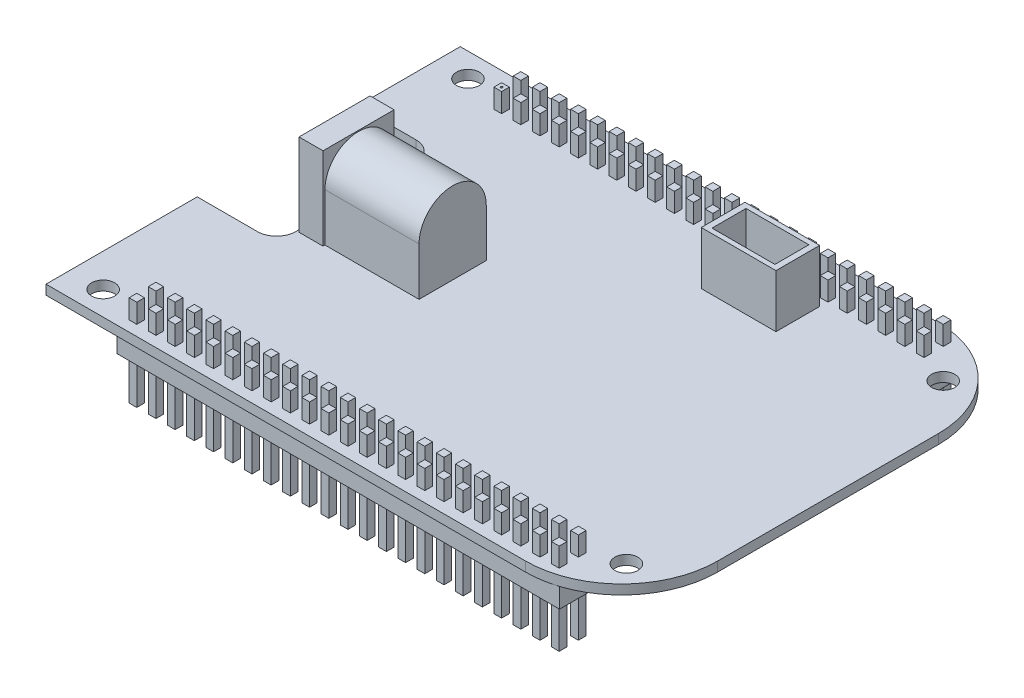
SolidWorks part; units mm, degrees
material "cape"
ref_plane "Front Plane" through (0, 0, 0) normal (0, 0, 1) x (1, 0, 0)
ref_plane "Top Plane" through (0, 0, 0) normal (0, 1, 0) x (1, 0, 0)
ref_plane "Right Plane" through (0, 0, 0) normal (1, 0, 0) x (0, 0, -1)
sketch "Sketch1" plane through (0, 0, 0) normal (0, 1, 0) x (1, 0, 0)
  line L0 (-86.36, 27.305) -> (0, 27.305) construction
  line L1 (-12.7, 0) -> (-80.01, 0)
  line L2 (0, 12.7) -> (0, 41.91)
  line L3 (-12.7, 54.61) -> (-80.01, 54.61)
  line L4 (-86.36, 6.35) -> (-86.36, 48.26)
  line L5 (-71.755, 51.435) -> (-71.755, 3.175) construction
  line L6 (-5.715, 6.35) -> (-5.715, 48.26) construction
  arc A0 (0, 12.7) -> (-12.7, 0) centre (-12.7, 12.7) cw
  arc A1 (0, 41.91) -> (-12.7, 54.61) centre (-12.7, 41.91) ccw
  arc A2 (-86.36, 6.35) -> (-80.01, 0) centre (-80.01, 6.35) ccw
  arc A3 (-86.36, 48.26) -> (-80.01, 54.61) centre (-80.01, 48.26) cw
  circle A4 centre (-71.755, 51.435) radius 1.524
  circle A5 centre (-71.755, 3.175) radius 1.524
  circle A6 centre (-5.715, 6.35) radius 1.524
  circle A7 centre (-5.715, 48.26) radius 1.524
  point P7 (0, 0)
  point P10 (0, 54.61)
  point P13 (-86.36, 0)
  point P26 (-5.715, 27.305)
  point P27 (-71.755, 27.305)
  dimension "D3" = 12.7
  dimension "D4" = 6.35
  dimension "D6" = 41.91
  dimension "D9" = 3.048
  dimension "D1" = 86.36
  dimension "D2" = 54.61
  dimension "D5" = 48.26
  dimension "D7" = 5.715
  dimension "D8" = 14.605
extrude "Boss-Extrude1" add sketch "Sketch1" along normal blind 1.27
sketch "Sketch2" plane through (0, 1.27, 0) normal (0, 1, 0) x (1, 0, 0)
  line L0 (-80.01, 0) -> (-12.7, 0) construction
  line L1 (-5.715, 6.35) -> (-71.755, 6.35) construction
  line L3 (-86.36, 48.26) -> (-86.36, 6.35) construction
  line L4 (-5.715, 48.26) -> (-5.715, 6.35) construction
  circle A2 centre (-5.715, 48.26) radius 1.524
  circle A3 centre (-5.715, 6.35) radius 1.524
  dimension "D2" = 41.91
  dimension "D3" = 6.35
  dimension "D5" = 80.645
sketch "Sketch3" plane through (0, 1.27, 0) normal (0, 1, 0) x (1, 0, 0)
  line L0 (-10.16, 48.895) -> (-10.16, 50.165) construction
  line L1 (-67.31, 53.975) -> (-8.89, 53.975) construction
  line L2 (-67.31, 53.975) -> (-67.31, 48.895) construction
  line L3 (-67.31, 48.895) -> (-8.89, 48.895) construction
  line L4 (-8.89, 53.975) -> (-8.89, 48.895) construction
  line L5 (-86.36, 27.305) -> (0, 27.305) construction
  line L6 (0, 12.7) -> (0, 41.91) construction
  line L7 (-66.548, 4.953) -> (-66.548, 3.937)
  line L8 (-66.548, 4.953) -> (-65.532, 4.953)
  line L9 (-10.16, 50.165) -> (-10.16, 52.705) construction
  line L10 (-10.16, 52.705) -> (-10.16, 53.975) construction
  line L11 (-13.208, 52.197) -> (-12.192, 52.197)
  line L12 (-10.668, 53.213) -> (-9.652, 53.213)
  line L13 (-10.668, 53.213) -> (-10.668, 52.197)
  line L14 (-10.668, 52.197) -> (-9.652, 52.197)
  line L15 (-9.652, 53.213) -> (-9.652, 52.197)
  line L16 (-10.668, 53.213) -> (-9.652, 52.197) construction
  line L17 (-10.668, 52.197) -> (-9.652, 53.213) construction
  line L18 (-10.668, 49.657) -> (-9.652, 49.657)
  line L19 (-10.668, 49.657) -> (-10.668, 50.673)
  line L20 (-10.668, 50.673) -> (-9.652, 50.673)
  line L21 (-9.652, 49.657) -> (-9.652, 50.673)
  line L22 (-10.668, 49.657) -> (-9.652, 50.673) construction
  line L23 (-10.668, 50.673) -> (-9.652, 49.657) construction
  line L24 (-13.208, 53.213) -> (-13.208, 52.197)
  line L25 (-13.208, 53.213) -> (-12.192, 53.213)
  line L26 (-12.192, 53.213) -> (-12.192, 52.197)
  line L27 (-13.208, 50.673) -> (-12.192, 50.673)
  line L28 (-12.192, 49.657) -> (-12.192, 50.673)
  line L29 (-13.208, 49.657) -> (-12.192, 49.657)
  line L30 (-13.208, 49.657) -> (-13.208, 50.673)
  line L31 (-15.748, 52.197) -> (-14.732, 52.197)
  line L32 (-15.748, 53.213) -> (-15.748, 52.197)
  line L33 (-15.748, 53.213) -> (-14.732, 53.213)
  line L34 (-14.732, 53.213) -> (-14.732, 52.197)
  line L35 (-15.748, 50.673) -> (-14.732, 50.673)
  line L36 (-14.732, 49.657) -> (-14.732, 50.673)
  line L37 (-15.748, 49.657) -> (-14.732, 49.657)
  line L38 (-15.748, 49.657) -> (-15.748, 50.673)
  line L39 (-18.288, 52.197) -> (-17.272, 52.197)
  line L40 (-18.288, 53.213) -> (-18.288, 52.197)
  line L41 (-18.288, 53.213) -> (-17.272, 53.213)
  line L42 (-17.272, 53.213) -> (-17.272, 52.197)
  line L43 (-18.288, 50.673) -> (-17.272, 50.673)
  line L44 (-17.272, 49.657) -> (-17.272, 50.673)
  line L45 (-18.288, 49.657) -> (-17.272, 49.657)
  line L46 (-18.288, 49.657) -> (-18.288, 50.673)
  line L47 (-20.828, 52.197) -> (-19.812, 52.197)
  line L48 (-20.828, 53.213) -> (-20.828, 52.197)
  line L49 (-20.828, 53.213) -> (-19.812, 53.213)
  line L50 (-19.812, 53.213) -> (-19.812, 52.197)
  line L51 (-20.828, 50.673) -> (-19.812, 50.673)
  line L52 (-19.812, 49.657) -> (-19.812, 50.673)
  line L53 (-20.828, 49.657) -> (-19.812, 49.657)
  line L54 (-20.828, 49.657) -> (-20.828, 50.673)
  line L55 (-23.368, 52.197) -> (-22.352, 52.197)
  line L56 (-23.368, 53.213) -> (-23.368, 52.197)
  line L57 (-23.368, 53.213) -> (-22.352, 53.213)
  line L58 (-22.352, 53.213) -> (-22.352, 52.197)
  line L59 (-23.368, 50.673) -> (-22.352, 50.673)
  line L60 (-22.352, 49.657) -> (-22.352, 50.673)
  line L61 (-23.368, 49.657) -> (-22.352, 49.657)
  line L62 (-23.368, 49.657) -> (-23.368, 50.673)
  line L63 (-25.908, 52.197) -> (-24.892, 52.197)
  line L64 (-25.908, 53.213) -> (-25.908, 52.197)
  line L65 (-25.908, 53.213) -> (-24.892, 53.213)
  line L66 (-24.892, 53.213) -> (-24.892, 52.197)
  line L67 (-25.908, 50.673) -> (-24.892, 50.673)
  line L68 (-24.892, 49.657) -> (-24.892, 50.673)
  line L69 (-25.908, 49.657) -> (-24.892, 49.657)
  line L70 (-25.908, 49.657) -> (-25.908, 50.673)
  line L71 (-28.448, 52.197) -> (-27.432, 52.197)
  line L72 (-28.448, 53.213) -> (-28.448, 52.197)
  line L73 (-28.448, 53.213) -> (-27.432, 53.213)
  line L74 (-27.432, 53.213) -> (-27.432, 52.197)
  line L75 (-28.448, 50.673) -> (-27.432, 50.673)
  line L76 (-27.432, 49.657) -> (-27.432, 50.673)
  line L77 (-28.448, 49.657) -> (-27.432, 49.657)
  line L78 (-28.448, 49.657) -> (-28.448, 50.673)
  line L79 (-30.988, 52.197) -> (-29.972, 52.197)
  line L80 (-30.988, 53.213) -> (-30.988, 52.197)
  line L81 (-30.988, 53.213) -> (-29.972, 53.213)
  line L82 (-29.972, 53.213) -> (-29.972, 52.197)
  line L83 (-30.988, 50.673) -> (-29.972, 50.673)
  line L84 (-29.972, 49.657) -> (-29.972, 50.673)
  line L85 (-30.988, 49.657) -> (-29.972, 49.657)
  line L86 (-30.988, 49.657) -> (-30.988, 50.673)
  line L87 (-33.528, 52.197) -> (-32.512, 52.197)
  line L88 (-33.528, 53.213) -> (-33.528, 52.197)
  line L89 (-33.528, 53.213) -> (-32.512, 53.213)
  line L90 (-32.512, 53.213) -> (-32.512, 52.197)
  line L91 (-33.528, 50.673) -> (-32.512, 50.673)
  line L92 (-32.512, 49.657) -> (-32.512, 50.673)
  line L93 (-33.528, 49.657) -> (-32.512, 49.657)
  line L94 (-33.528, 49.657) -> (-33.528, 50.673)
  line L95 (-36.068, 52.197) -> (-35.052, 52.197)
  line L96 (-36.068, 53.213) -> (-36.068, 52.197)
  line L97 (-36.068, 53.213) -> (-35.052, 53.213)
  line L98 (-35.052, 53.213) -> (-35.052, 52.197)
  line L99 (-36.068, 50.673) -> (-35.052, 50.673)
  line L100 (-35.052, 49.657) -> (-35.052, 50.673)
  line L101 (-36.068, 49.657) -> (-35.052, 49.657)
  line L102 (-36.068, 49.657) -> (-36.068, 50.673)
  line L103 (-38.608, 52.197) -> (-37.592, 52.197)
  line L104 (-38.608, 53.213) -> (-38.608, 52.197)
  line L105 (-38.608, 53.213) -> (-37.592, 53.213)
  line L106 (-37.592, 53.213) -> (-37.592, 52.197)
  line L107 (-38.608, 50.673) -> (-37.592, 50.673)
  line L108 (-37.592, 49.657) -> (-37.592, 50.673)
  line L109 (-38.608, 49.657) -> (-37.592, 49.657)
  line L110 (-38.608, 49.657) -> (-38.608, 50.673)
  line L111 (-41.148, 52.197) -> (-40.132, 52.197)
  line L112 (-41.148, 53.213) -> (-41.148, 52.197)
  line L113 (-41.148, 53.213) -> (-40.132, 53.213)
  line L114 (-40.132, 53.213) -> (-40.132, 52.197)
  line L115 (-41.148, 50.673) -> (-40.132, 50.673)
  line L116 (-40.132, 49.657) -> (-40.132, 50.673)
  line L117 (-41.148, 49.657) -> (-40.132, 49.657)
  line L118 (-41.148, 49.657) -> (-41.148, 50.673)
  line L119 (-43.688, 52.197) -> (-42.672, 52.197)
  line L120 (-43.688, 53.213) -> (-43.688, 52.197)
  line L121 (-43.688, 53.213) -> (-42.672, 53.213)
  line L122 (-42.672, 53.213) -> (-42.672, 52.197)
  line L123 (-43.688, 50.673) -> (-42.672, 50.673)
  line L124 (-42.672, 49.657) -> (-42.672, 50.673)
  line L125 (-43.688, 49.657) -> (-42.672, 49.657)
  line L126 (-43.688, 49.657) -> (-43.688, 50.673)
  line L127 (-46.228, 52.197) -> (-45.212, 52.197)
  line L128 (-46.228, 53.213) -> (-46.228, 52.197)
  line L129 (-46.228, 53.213) -> (-45.212, 53.213)
  line L130 (-45.212, 53.213) -> (-45.212, 52.197)
  line L131 (-46.228, 50.673) -> (-45.212, 50.673)
  line L132 (-45.212, 49.657) -> (-45.212, 50.673)
  line L133 (-46.228, 49.657) -> (-45.212, 49.657)
  line L134 (-46.228, 49.657) -> (-46.228, 50.673)
  line L135 (-48.768, 52.197) -> (-47.752, 52.197)
  line L136 (-48.768, 53.213) -> (-48.768, 52.197)
  line L137 (-48.768, 53.213) -> (-47.752, 53.213)
  line L138 (-47.752, 53.213) -> (-47.752, 52.197)
  line L139 (-48.768, 50.673) -> (-47.752, 50.673)
  line L140 (-47.752, 49.657) -> (-47.752, 50.673)
  line L141 (-48.768, 49.657) -> (-47.752, 49.657)
  line L142 (-48.768, 49.657) -> (-48.768, 50.673)
  line L143 (-51.308, 52.197) -> (-50.292, 52.197)
  line L144 (-51.308, 53.213) -> (-51.308, 52.197)
  line L145 (-51.308, 53.213) -> (-50.292, 53.213)
  line L146 (-50.292, 53.213) -> (-50.292, 52.197)
  line L147 (-51.308, 50.673) -> (-50.292, 50.673)
  line L148 (-50.292, 49.657) -> (-50.292, 50.673)
  line L149 (-51.308, 49.657) -> (-50.292, 49.657)
  line L150 (-51.308, 49.657) -> (-51.308, 50.673)
  line L151 (-53.848, 52.197) -> (-52.832, 52.197)
  line L152 (-53.848, 53.213) -> (-53.848, 52.197)
  line L153 (-53.848, 53.213) -> (-52.832, 53.213)
  line L154 (-52.832, 53.213) -> (-52.832, 52.197)
  line L155 (-53.848, 50.673) -> (-52.832, 50.673)
  line L156 (-52.832, 49.657) -> (-52.832, 50.673)
  line L157 (-53.848, 49.657) -> (-52.832, 49.657)
  line L158 (-53.848, 49.657) -> (-53.848, 50.673)
  line L159 (-56.388, 52.197) -> (-55.372, 52.197)
  line L160 (-56.388, 53.213) -> (-56.388, 52.197)
  line L161 (-56.388, 53.213) -> (-55.372, 53.213)
  line L162 (-55.372, 53.213) -> (-55.372, 52.197)
  line L163 (-56.388, 50.673) -> (-55.372, 50.673)
  line L164 (-55.372, 49.657) -> (-55.372, 50.673)
  line L165 (-56.388, 49.657) -> (-55.372, 49.657)
  line L166 (-56.388, 49.657) -> (-56.388, 50.673)
  line L167 (-58.928, 52.197) -> (-57.912, 52.197)
  line L168 (-58.928, 53.213) -> (-58.928, 52.197)
  line L169 (-58.928, 53.213) -> (-57.912, 53.213)
  line L170 (-57.912, 53.213) -> (-57.912, 52.197)
  line L171 (-58.928, 50.673) -> (-57.912, 50.673)
  line L172 (-57.912, 49.657) -> (-57.912, 50.673)
  line L173 (-58.928, 49.657) -> (-57.912, 49.657)
  line L174 (-58.928, 49.657) -> (-58.928, 50.673)
  line L175 (-61.468, 52.197) -> (-60.452, 52.197)
  line L176 (-61.468, 53.213) -> (-61.468, 52.197)
  line L177 (-61.468, 53.213) -> (-60.452, 53.213)
  line L178 (-60.452, 53.213) -> (-60.452, 52.197)
  line L179 (-61.468, 50.673) -> (-60.452, 50.673)
  line L180 (-60.452, 49.657) -> (-60.452, 50.673)
  line L181 (-61.468, 49.657) -> (-60.452, 49.657)
  line L182 (-61.468, 49.657) -> (-61.468, 50.673)
  line L183 (-64.008, 52.197) -> (-62.992, 52.197)
  line L184 (-64.008, 53.213) -> (-64.008, 52.197)
  line L185 (-64.008, 53.213) -> (-62.992, 53.213)
  line L186 (-62.992, 53.213) -> (-62.992, 52.197)
  line L187 (-64.008, 50.673) -> (-62.992, 50.673)
  line L188 (-62.992, 49.657) -> (-62.992, 50.673)
  line L189 (-64.008, 49.657) -> (-62.992, 49.657)
  line L190 (-64.008, 49.657) -> (-64.008, 50.673)
  line L191 (-66.548, 52.197) -> (-65.532, 52.197)
  line L192 (-66.548, 53.213) -> (-66.548, 52.197)
  line L193 (-66.548, 53.213) -> (-65.532, 53.213)
  line L194 (-65.532, 53.213) -> (-65.532, 52.197)
  line L195 (-66.548, 50.673) -> (-65.532, 50.673)
  line L196 (-65.532, 49.657) -> (-65.532, 50.673)
  line L197 (-66.548, 49.657) -> (-65.532, 49.657)
  line L198 (-66.548, 49.657) -> (-66.548, 50.673)
  line L199 (-66.548, 49.657) -> (-65.532, 50.673) construction
  line L200 (-86.36, 48.26) -> (-86.36, 6.35) construction
  line L201 (-65.532, 4.953) -> (-65.532, 3.937)
  line L202 (-12.7, 54.61) -> (-80.01, 54.61) construction
  line L203 (-66.548, 3.937) -> (-65.532, 3.937)
  line L204 (-65.532, 1.397) -> (-65.532, 2.413)
  line L205 (-66.548, 1.397) -> (-65.532, 1.397)
  line L206 (-66.548, 1.397) -> (-66.548, 2.413)
  line L207 (-66.548, 2.413) -> (-65.532, 2.413)
  line L208 (-64.008, 4.953) -> (-64.008, 3.937)
  line L209 (-64.008, 4.953) -> (-62.992, 4.953)
  line L210 (-62.992, 4.953) -> (-62.992, 3.937)
  line L211 (-64.008, 3.937) -> (-62.992, 3.937)
  line L212 (-62.992, 1.397) -> (-62.992, 2.413)
  line L213 (-64.008, 1.397) -> (-62.992, 1.397)
  line L214 (-64.008, 1.397) -> (-64.008, 2.413)
  line L215 (-64.008, 2.413) -> (-62.992, 2.413)
  line L216 (-61.468, 4.953) -> (-61.468, 3.937)
  line L217 (-61.468, 4.953) -> (-60.452, 4.953)
  line L218 (-60.452, 4.953) -> (-60.452, 3.937)
  line L219 (-61.468, 3.937) -> (-60.452, 3.937)
  line L220 (-60.452, 1.397) -> (-60.452, 2.413)
  line L221 (-61.468, 1.397) -> (-60.452, 1.397)
  line L222 (-61.468, 1.397) -> (-61.468, 2.413)
  line L223 (-61.468, 2.413) -> (-60.452, 2.413)
  line L224 (-58.928, 4.953) -> (-58.928, 3.937)
  line L225 (-58.928, 4.953) -> (-57.912, 4.953)
  line L226 (-57.912, 4.953) -> (-57.912, 3.937)
  line L227 (-58.928, 3.937) -> (-57.912, 3.937)
  line L228 (-57.912, 1.397) -> (-57.912, 2.413)
  line L229 (-58.928, 1.397) -> (-57.912, 1.397)
  line L230 (-58.928, 1.397) -> (-58.928, 2.413)
  line L231 (-58.928, 2.413) -> (-57.912, 2.413)
  line L232 (-56.388, 4.953) -> (-56.388, 3.937)
  line L233 (-56.388, 4.953) -> (-55.372, 4.953)
  line L234 (-55.372, 4.953) -> (-55.372, 3.937)
  line L235 (-56.388, 3.937) -> (-55.372, 3.937)
  line L236 (-55.372, 1.397) -> (-55.372, 2.413)
  line L237 (-56.388, 1.397) -> (-55.372, 1.397)
  line L238 (-56.388, 1.397) -> (-56.388, 2.413)
  line L239 (-56.388, 2.413) -> (-55.372, 2.413)
  line L240 (-53.848, 4.953) -> (-53.848, 3.937)
  line L241 (-53.848, 4.953) -> (-52.832, 4.953)
  line L242 (-52.832, 4.953) -> (-52.832, 3.937)
  line L243 (-53.848, 3.937) -> (-52.832, 3.937)
  line L244 (-52.832, 1.397) -> (-52.832, 2.413)
  line L245 (-53.848, 1.397) -> (-52.832, 1.397)
  line L246 (-53.848, 1.397) -> (-53.848, 2.413)
  line L247 (-53.848, 2.413) -> (-52.832, 2.413)
  line L248 (-51.308, 4.953) -> (-51.308, 3.937)
  line L249 (-51.308, 4.953) -> (-50.292, 4.953)
  line L250 (-50.292, 4.953) -> (-50.292, 3.937)
  line L251 (-51.308, 3.937) -> (-50.292, 3.937)
  line L252 (-50.292, 1.397) -> (-50.292, 2.413)
  line L253 (-51.308, 1.397) -> (-50.292, 1.397)
  line L254 (-51.308, 1.397) -> (-51.308, 2.413)
  line L255 (-51.308, 2.413) -> (-50.292, 2.413)
  line L256 (-48.768, 4.953) -> (-48.768, 3.937)
  line L257 (-48.768, 4.953) -> (-47.752, 4.953)
  line L258 (-47.752, 4.953) -> (-47.752, 3.937)
  line L259 (-48.768, 3.937) -> (-47.752, 3.937)
  line L260 (-47.752, 1.397) -> (-47.752, 2.413)
  line L261 (-48.768, 1.397) -> (-47.752, 1.397)
  line L262 (-48.768, 1.397) -> (-48.768, 2.413)
  line L263 (-48.768, 2.413) -> (-47.752, 2.413)
  line L264 (-46.228, 4.953) -> (-46.228, 3.937)
  line L265 (-46.228, 4.953) -> (-45.212, 4.953)
  line L266 (-45.212, 4.953) -> (-45.212, 3.937)
  line L267 (-46.228, 3.937) -> (-45.212, 3.937)
  line L268 (-45.212, 1.397) -> (-45.212, 2.413)
  line L269 (-46.228, 1.397) -> (-45.212, 1.397)
  line L270 (-46.228, 1.397) -> (-46.228, 2.413)
  line L271 (-46.228, 2.413) -> (-45.212, 2.413)
  line L272 (-43.688, 4.953) -> (-43.688, 3.937)
  line L273 (-43.688, 4.953) -> (-42.672, 4.953)
  line L274 (-42.672, 4.953) -> (-42.672, 3.937)
  line L275 (-43.688, 3.937) -> (-42.672, 3.937)
  line L276 (-42.672, 1.397) -> (-42.672, 2.413)
  line L277 (-43.688, 1.397) -> (-42.672, 1.397)
  line L278 (-43.688, 1.397) -> (-43.688, 2.413)
  line L279 (-43.688, 2.413) -> (-42.672, 2.413)
  line L280 (-41.148, 4.953) -> (-41.148, 3.937)
  line L281 (-41.148, 4.953) -> (-40.132, 4.953)
  line L282 (-40.132, 4.953) -> (-40.132, 3.937)
  line L283 (-41.148, 3.937) -> (-40.132, 3.937)
  line L284 (-40.132, 1.397) -> (-40.132, 2.413)
  line L285 (-41.148, 1.397) -> (-40.132, 1.397)
  line L286 (-41.148, 1.397) -> (-41.148, 2.413)
  line L287 (-41.148, 2.413) -> (-40.132, 2.413)
  line L288 (-38.608, 4.953) -> (-38.608, 3.937)
  line L289 (-38.608, 4.953) -> (-37.592, 4.953)
  line L290 (-37.592, 4.953) -> (-37.592, 3.937)
  line L291 (-38.608, 3.937) -> (-37.592, 3.937)
  line L292 (-37.592, 1.397) -> (-37.592, 2.413)
  line L293 (-38.608, 1.397) -> (-37.592, 1.397)
  line L294 (-38.608, 1.397) -> (-38.608, 2.413)
  line L295 (-38.608, 2.413) -> (-37.592, 2.413)
  line L296 (-36.068, 4.953) -> (-36.068, 3.937)
  line L297 (-36.068, 4.953) -> (-35.052, 4.953)
  line L298 (-35.052, 4.953) -> (-35.052, 3.937)
  line L299 (-36.068, 3.937) -> (-35.052, 3.937)
  line L300 (-35.052, 1.397) -> (-35.052, 2.413)
  line L301 (-36.068, 1.397) -> (-35.052, 1.397)
  line L302 (-36.068, 1.397) -> (-36.068, 2.413)
  line L303 (-36.068, 2.413) -> (-35.052, 2.413)
  line L304 (-33.528, 4.953) -> (-33.528, 3.937)
  line L305 (-33.528, 4.953) -> (-32.512, 4.953)
  line L306 (-32.512, 4.953) -> (-32.512, 3.937)
  line L307 (-33.528, 3.937) -> (-32.512, 3.937)
  line L308 (-32.512, 1.397) -> (-32.512, 2.413)
  line L309 (-33.528, 1.397) -> (-32.512, 1.397)
  line L310 (-33.528, 1.397) -> (-33.528, 2.413)
  line L311 (-33.528, 2.413) -> (-32.512, 2.413)
  line L312 (-30.988, 4.953) -> (-30.988, 3.937)
  line L313 (-30.988, 4.953) -> (-29.972, 4.953)
  line L314 (-29.972, 4.953) -> (-29.972, 3.937)
  line L315 (-30.988, 3.937) -> (-29.972, 3.937)
  line L316 (-29.972, 1.397) -> (-29.972, 2.413)
  line L317 (-30.988, 1.397) -> (-29.972, 1.397)
  line L318 (-30.988, 1.397) -> (-30.988, 2.413)
  line L319 (-30.988, 2.413) -> (-29.972, 2.413)
  line L320 (-28.448, 4.953) -> (-28.448, 3.937)
  line L321 (-28.448, 4.953) -> (-27.432, 4.953)
  line L322 (-27.432, 4.953) -> (-27.432, 3.937)
  line L323 (-28.448, 3.937) -> (-27.432, 3.937)
  line L324 (-27.432, 1.397) -> (-27.432, 2.413)
  line L325 (-28.448, 1.397) -> (-27.432, 1.397)
  line L326 (-28.448, 1.397) -> (-28.448, 2.413)
  line L327 (-28.448, 2.413) -> (-27.432, 2.413)
  line L328 (-25.908, 4.953) -> (-25.908, 3.937)
  line L329 (-25.908, 4.953) -> (-24.892, 4.953)
  line L330 (-24.892, 4.953) -> (-24.892, 3.937)
  line L331 (-25.908, 3.937) -> (-24.892, 3.937)
  line L332 (-24.892, 1.397) -> (-24.892, 2.413)
  line L333 (-25.908, 1.397) -> (-24.892, 1.397)
  line L334 (-25.908, 1.397) -> (-25.908, 2.413)
  line L335 (-25.908, 2.413) -> (-24.892, 2.413)
  line L336 (-23.368, 4.953) -> (-23.368, 3.937)
  line L337 (-23.368, 4.953) -> (-22.352, 4.953)
  line L338 (-22.352, 4.953) -> (-22.352, 3.937)
  line L339 (-23.368, 3.937) -> (-22.352, 3.937)
  line L340 (-22.352, 1.397) -> (-22.352, 2.413)
  line L341 (-23.368, 1.397) -> (-22.352, 1.397)
  line L342 (-23.368, 1.397) -> (-23.368, 2.413)
  line L343 (-23.368, 2.413) -> (-22.352, 2.413)
  line L344 (-20.828, 4.953) -> (-20.828, 3.937)
  line L345 (-20.828, 4.953) -> (-19.812, 4.953)
  line L346 (-19.812, 4.953) -> (-19.812, 3.937)
  line L347 (-20.828, 3.937) -> (-19.812, 3.937)
  line L348 (-19.812, 1.397) -> (-19.812, 2.413)
  line L349 (-20.828, 1.397) -> (-19.812, 1.397)
  line L350 (-20.828, 1.397) -> (-20.828, 2.413)
  line L351 (-20.828, 2.413) -> (-19.812, 2.413)
  line L352 (-18.288, 4.953) -> (-18.288, 3.937)
  line L353 (-18.288, 4.953) -> (-17.272, 4.953)
  line L354 (-17.272, 4.953) -> (-17.272, 3.937)
  line L355 (-18.288, 3.937) -> (-17.272, 3.937)
  line L356 (-17.272, 1.397) -> (-17.272, 2.413)
  line L357 (-18.288, 1.397) -> (-17.272, 1.397)
  line L358 (-18.288, 1.397) -> (-18.288, 2.413)
  line L359 (-18.288, 2.413) -> (-17.272, 2.413)
  line L360 (-15.748, 4.953) -> (-15.748, 3.937)
  line L361 (-15.748, 4.953) -> (-14.732, 4.953)
  line L362 (-14.732, 4.953) -> (-14.732, 3.937)
  line L363 (-15.748, 3.937) -> (-14.732, 3.937)
  line L364 (-14.732, 1.397) -> (-14.732, 2.413)
  line L365 (-15.748, 1.397) -> (-14.732, 1.397)
  line L366 (-15.748, 1.397) -> (-15.748, 2.413)
  line L367 (-15.748, 2.413) -> (-14.732, 2.413)
  line L368 (-13.208, 4.953) -> (-13.208, 3.937)
  line L369 (-13.208, 4.953) -> (-12.192, 4.953)
  line L370 (-12.192, 4.953) -> (-12.192, 3.937)
  line L371 (-13.208, 3.937) -> (-12.192, 3.937)
  line L372 (-12.192, 1.397) -> (-12.192, 2.413)
  line L373 (-13.208, 1.397) -> (-12.192, 1.397)
  line L374 (-13.208, 1.397) -> (-13.208, 2.413)
  line L375 (-9.652, 4.953) -> (-9.652, 3.937)
  line L376 (-10.668, 3.937) -> (-9.652, 3.937)
  line L377 (-10.668, 4.953) -> (-10.668, 3.937)
  line L378 (-10.668, 4.953) -> (-9.652, 4.953)
  line L379 (-9.652, 1.397) -> (-9.652, 2.413)
  line L380 (-10.668, 2.413) -> (-9.652, 2.413)
  line L381 (-10.668, 1.397) -> (-10.668, 2.413)
  line L382 (-10.668, 1.397) -> (-9.652, 1.397)
  line L383 (-13.208, 2.413) -> (-12.192, 2.413)
  line L384 (-8.89, 0.635) -> (-8.89, 5.715) construction
  line L385 (-67.31, 5.715) -> (-8.89, 5.715) construction
  line L386 (-67.31, 0.635) -> (-67.31, 5.715) construction
  line L387 (-67.31, 0.635) -> (-8.89, 0.635) construction
  circle A0 centre (-66.04, 50.165) radius 0.1361
  dimension "D1" = 1.016
  dimension "D2" = 2.54
  dimension "D3" = 5.08
  dimension "D4" = 58.42
  dimension "D5" = 1.27
  dimension "D7" = 20.32
  dimension "D8" = 0.635
  dimension "D6" = 23
extrude "Boss-Extrude2" add sketch "Sketch3" along normal blind 2.54 and the other way blind 9.525
sketch "Sketch14" plane through (0, 1.27, 0) normal (0, 1, 0) x (1, 0, 0)
  line L0 (-75.9484, 54.61) -> (-75.9484, 41.0079)
  line L1 (-12.7, 54.61) -> (-80.01, 54.61) construction
  line L2 (-65.6397, 38.4679) -> (-65.6397, 22.5426)
  line L3 (-76.1396, 20.0026) -> (-76.1396, 0)
  line L4 (-80.01, 0) -> (-12.7, 0) construction
  line L5 (-75.9484, 54.61) -> (-105.3672, 54.61)
  line L6 (-105.3672, 54.61) -> (-105.3672, 0)
  line L7 (-105.3672, 0) -> (-76.1396, 0)
  line L8 (0, 12.7) -> (0, 41.91) construction
  line L9 (-75.9484, 41.0079) -> (-68.1797, 41.0079)
  line L10 (-76.1396, 20.0026) -> (-68.1797, 20.0026)
  arc A0 (-68.1797, 41.0079) -> (-65.6397, 38.4679) centre (-68.1797, 38.4679) cw
  arc A1 (-68.1797, 20.0026) -> (-65.6397, 22.5426) centre (-68.1797, 22.5426) ccw
  dimension "D1" = 75.9484
  dimension "D2" = 2.54
  dimension "D3" = 76.1396
  dimension "D4" = 65.6397
  dimension "D5" = 13.6021
  dimension "D6" = 20.0026
extrude "Cut-Extrude5" cut sketch "Sketch14" against normal through all
sketch "Sketch9" plane through (0, 1.27, 0) normal (0, 1, 0) x (1, 0, 0)
  line L1 (-49.7208, 22.9284) -> (-65.3418, 22.9284)
  line L2 (-49.7208, 22.9284) -> (-49.7208, 31.8184)
  line L3 (-49.7208, 31.8184) -> (-65.3418, 31.8184)
  line L4 (-65.3418, 22.9284) -> (-65.3418, 31.8184)
  dimension "D1" = 8.89
  dimension "D2" = 15.621
extrude "Boss-Extrude6" add sketch "Sketch9" along normal blind 6.35
sketch "Sketch10" plane through (-65.3418, 0, 0) normal (-1, 0, 0) x (0, 0, 1)
  line L0 (-31.8184, 7.62) -> (-22.9284, 7.62) construction
  circle A0 centre (-27.3734, 7.62) radius 4.445
  circle A1 centre (-27.3734, 7.62) radius 3.4925
  circle A2 centre (-27.3734, 7.62) radius 0.635
  line M3 (-22.9284, 7.62) -> (-31.8184, 7.62)
  dimension "D1" = 1.27
  dimension "D2" = 6.985
extrude "Boss-Extrude7" add sketch "Sketch10" along direction (1, 0, 0) on the side against the normal up to surface (15.621 mm away) contours A1 A0 M3 | A1 A0 M3 | A2 M3 | A2 A1 M3 region at (-65.3418, 7.7194, -23.4047) region at (-65.3418, 3.2744, -27.3734) region at (-65.3418, 9.1437, -27.3734) region at (-65.3418, 7.8895, -27.3734) up to face at (-49.7208, 4.445, -27.3734)
sketch "Sketch11" plane through (-65.3418, 0, 0) normal (-1, 0, 0) x (0, 0, 1)
  line L0 (-31.8184, 7.62) -> (-31.8184, 1.27) construction
  line L1 (-22.6744, 1.27) -> (-32.0724, 1.27)
  line L2 (-22.6744, 1.27) -> (-22.6744, 12.1969)
  line L3 (-22.6744, 12.1969) -> (-32.0724, 12.1969)
  line L4 (-32.0724, 1.27) -> (-32.0724, 12.1969)
  line L5 (-22.6744, 1.27) -> (-32.0724, 12.1969) construction
  line L6 (-22.6744, 12.1969) -> (-32.0724, 1.27) construction
  line L7 (-22.5426, 1.27) -> (-38.4679, 1.27) construction
  arc A0 (-22.9284, 7.62) -> (-31.8184, 7.62) centre (-27.3734, 7.62) ccw construction
  point P0 (-27.3734, 6.7335)
  point P8 (-27.3734, 7.62)
  point P11 (-27.3734, 12.065)
  dimension "D1" = 0.254
  dimension "D2" = 0.1319
extrude "Boss-Extrude8" add sketch "Sketch11" against normal blind 3.175
extrude "Cut-Extrude4" cut sketch "Sketch10<3>" against normal blind 12.7 contours A2 A1 M3 | A2 A1 M3 region at (-65.3418, 9.1437, -27.3734) region at (-65.3418, 6.0963, -27.3734)
sketch "Sketch10<3>" plane through (-65.3418, 0, 0) normal (-1, 0, 0) x (0, 0, 1) same geometry as "Sketch10"
fillet "Fillet1" radius 0.635 1 edges at (-65.3418, 7.62, -26.7384)
ref_plane "Vertical Plane" through (0, 0, -27.305) normal (0, 0, 1) x (1, 0, 0)
ref_plane "Plane1" through (0, 1.27, 0) normal (0, 1, 0) x (1, 0, 0)
sketch "Sketch16" plane through (0, 0, 0) normal (0, -1, 0) x (1, 0, 0)
  line L0 (-1000, -27.305) -> (49000, -27.305) construction
  line L1 (-67.3219, -0.5423) -> (-8.7493, -0.5423)
  line L2 (-67.3219, -0.5423) -> (-67.3219, -5.897)
  line L3 (-67.3219, -5.897) -> (-8.7493, -5.897)
  line L4 (-8.7493, -0.5423) -> (-8.7493, -5.897)
  line L5 (0, -12.7) -> (0, -41.91) construction
  line L6 (-8.7493, -54.0677) -> (-8.7493, -48.713)
  line L7 (-67.3219, -48.713) -> (-8.7493, -48.713)
  line L8 (-67.3219, -54.0677) -> (-67.3219, -48.713)
  line L9 (-67.3219, -54.0677) -> (-8.7493, -54.0677)
  point P9 (0, -27.305)
extrude "Boss-Extrude9" add sketch "Sketch16" along normal blind 2.54
sketch "Sketch17" plane through (0, 1.27, 0) normal (0, 1, 0) x (1, 0, 0)
  line L0 (-12.7, 54.61) -> (-75.9484, 54.61) construction
  line L1 (-32.29, 42.83) -> (-22.41, 42.83)
  line L2 (-32.29, 42.83) -> (-32.29, 48.61)
  line L3 (-32.29, 48.61) -> (-22.41, 48.61)
  line L4 (-22.41, 42.83) -> (-22.41, 48.61)
  line L5 (-32.29, 42.83) -> (-22.41, 48.61) construction
  line L6 (-32.29, 48.61) -> (-22.41, 42.83) construction
  line L7 (-31.51, 43.47) -> (-23.19, 43.47)
  line L8 (-31.51, 43.47) -> (-31.51, 47.97)
  line L9 (-31.51, 47.97) -> (-23.19, 47.97)
  line L10 (-23.19, 43.47) -> (-23.19, 47.97)
  line L11 (-31.51, 43.47) -> (-23.19, 47.97) construction
  line L12 (-31.51, 47.97) -> (-23.19, 43.47) construction
  line L13 (0, 12.7) -> (0, 41.91) construction
  point P0 (-27.35, 45.72)
  point P5 (-27.35, 45.72)
  dimension "D1" = 0.64
  dimension "D2" = 0.78
  dimension "D3" = 6
  dimension "D4" = 22.41
  dimension "D5" = 9.88
  dimension "D6" = 5.78
extrude "Boss-Extrude10" add sketch "Sketch17" along normal blind 7
